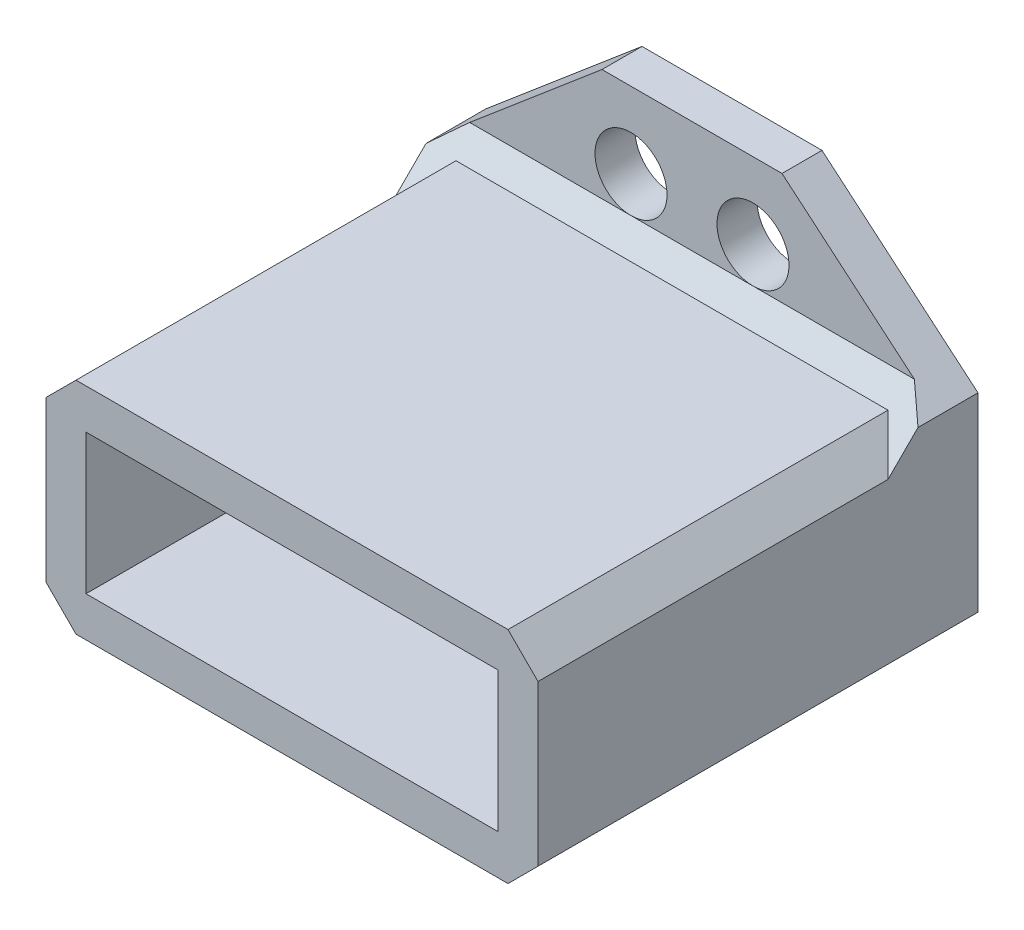
SolidWorks part; units mm, degrees
ref_plane "Front Plane" through (0, 0, 0) normal (0, 0, 1) x (1, 0, 0)
ref_plane "Top Plane" through (0, 0, 0) normal (0, 1, 0) x (1, 0, 0)
ref_plane "Right Plane" through (0, 0, 0) normal (1, 0, 0) x (0, 0, -1)
sketch "Esboço1" plane through (0, 0, 0) normal (0, 0, 1) x (1, 0, 0)
  line L0 (-10.3, 3.5) -> (10.3, 3.5)
  line L1 (-10, 3.2) -> (10, 3.2) construction
  line L2 (-10, 3.2) -> (-10, -3.2) construction
  line L3 (-10, -3.2) -> (10, -3.2) construction
  line L4 (10, 3.2) -> (10, -3.2) construction
  line L5 (10.3, 3.5) -> (10.3, -3.5)
  line L6 (-10.3, -3.5) -> (10.3, -3.5)
  line L7 (-10.3, 3.5) -> (-10.3, -3.5)
  line L8 (-12.3, 5.5) -> (-12.3, -5.5)
  line L9 (-12.3, -5.5) -> (12.3, -5.5)
  line L10 (12.3, 5.5) -> (12.3, -5.5)
  line L11 (-12.3, 5.5) -> (12.3, 5.5)
  point P4 (0, 3.2)
  point P6 (-10, 0)
  dimension "D1" = 6.4
  dimension "D2" = 20
  dimension "D3" = 0.3
  dimension "D4" = 2
extrude "Ressalto-extrusão1" add sketch "Esboço1" along normal mid plane 20
sketch "Esboço2" plane through (0, 0, -10) normal (0, 0, -1) x (-1, 0, 0)
  line L0 (-12.3, -5.5) -> (-12.3, 5.5)
  line L2 (12.3, 5.5) -> (12.3, -5.5)
  line L3 (12.3, -5.5) -> (-12.3, -5.5)
  line L12 (10.3, 3.5) -> (-10.3, 3.5)
  line L13 (10.3, -3.5) -> (10.3, 3.5)
  line L14 (-10.3, -3.5) -> (10.3, -3.5)
  line L15 (-10.3, 3.5) -> (-10.3, -3.5)
  line L16 (10.3, 3.5) -> (-10.3, 3.5)
  line L17 (10.3, -3.5) -> (10.3, 3.5)
  line L18 (-10.3, -3.5) -> (10.3, -3.5)
  line L19 (-10.3, 3.5) -> (-10.3, -3.5)
  line L21 (0, 9.68) -> (0, -9.68) construction
  line L23 (-12.3, 5.5) -> (12.3, 5.5) construction
  line L24 (12.3, 5.5) -> (4.5, 12.1)
  line L25 (4.5, 12.1) -> (-4.5, 12.1)
  line L26 (-4.5, 12.1) -> (-12.3, 5.5)
  line L27 (-12.3, 5.5) -> (12.3, 5.5) construction
  circle A0 centre (-3.05, 8.3) radius 1.5 construction
  circle A2 centre (-3.05, 8.3) radius 1.8
  circle A3 centre (3.05, 8.3) radius 1.8
  point P1 (0, 12.1)
  dimension "D3" = 2.5
  dimension "D4" = 1
  dimension "D5" = 3
  dimension "D6" = 2
  dimension "D8" = 6.1
  dimension "D7" = 9
  dimension "D1" = 0.3
  dimension "D2" = 0
extrude "Ressalto-extrusão2" add sketch "Esboço2" along normal blind 2
chamfer "Chanfro4" distance 1 angle 45 1 edges at (0, 5.5, -10)
chamfer "Chanfro2" distance 1.5 angle 45 4 edges at (-12.3, -5.5, -1) (12.3, -5.5, -1) (12.3, 5.5, 0.5) (-12.3, 5.5, 0.5)
ref_plane "Plano1" through (0, 0, -0.75) normal (0, 0, 1) x (1, 0, 0)
sketch "Esboço3" plane through (0, 0, -0.75) normal (0, 0, 1) x (1, 0, 0)
  line L0 (10.3, -3.5) -> (-10.3, -3.5) construction
  line L1 (-6.8268, 3.5) -> (-3.1732, 3.5)
  line L2 (-6.8268, 3.5) -> (-6.8268, -3.5)
  line L3 (-6.8268, -3.5) -> (-3.1732, -3.5)
  line L4 (-3.1732, 3.5) -> (-3.1732, -3.5)
  line L6 (-10.3, 3.5) -> (10.3, 3.5) construction
  line L8 (-3.1732, -3.2) -> (-3.1732, 3.2) construction
  line L9 (-6.8268, 3.2) -> (-6.8268, -3.2) construction
  line L10 (3.1732, 3.2) -> (3.1732, -3.2) construction
  line L11 (3.1732, 3.5) -> (6.8268, 3.5)
  line L12 (3.1732, 3.5) -> (3.1732, -3.5)
  line L13 (3.1732, -3.5) -> (6.8268, -3.5)
  line L14 (6.8268, 3.5) -> (6.8268, -3.5)
  line L15 (6.8268, -3.2) -> (6.8268, 3.2) construction
extrude "Ressalto-extrusão3" add sketch "Esboço3" against normal blind 3
fillet "Filete3" radius 2 4 edges at (5, 3.5, -3.75) (5, -3.5, -3.75) (-5, 3.5, -3.75) (-5, -3.5, -3.75)
